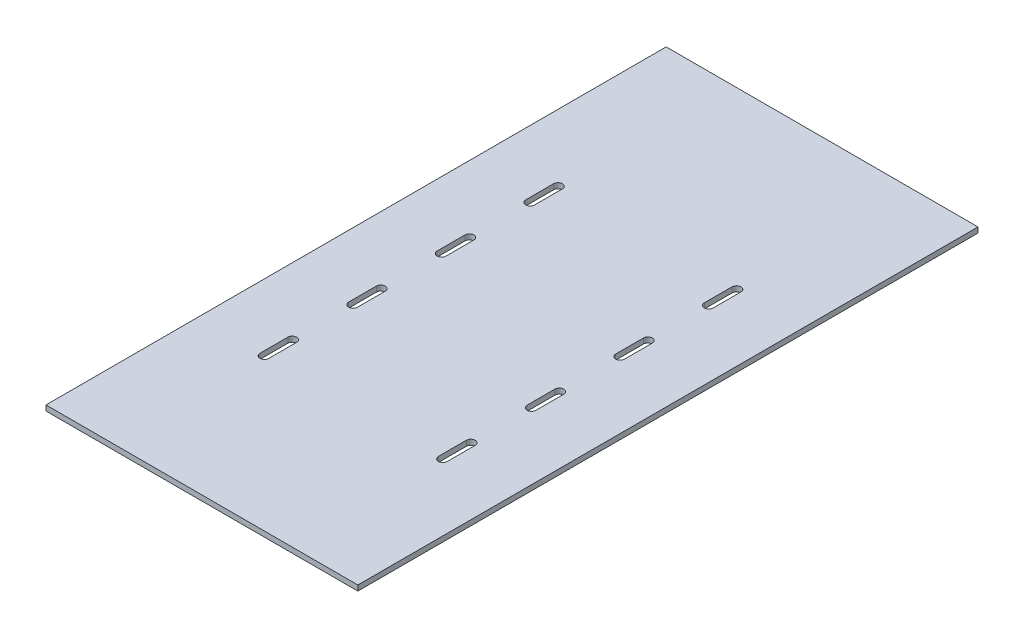
SolidWorks part; units mm, degrees
ref_plane "Front Plane" through (0, 0, 0) normal (0, 0, 1) x (1, 0, 0)
ref_plane "Top Plane" through (0, 0, 0) normal (0, 1, 0) x (1, 0, 0)
ref_plane "Right Plane" through (0, 0, 0) normal (1, 0, 0) x (0, 0, -1)
sketch "Sketch1" plane through (0, 0, 0) normal (0, 1, 0) x (1, 0, 0)
  line L1 (0, 0) -> (176, 0)
  line L2 (0, 0) -> (0, 350)
  line L3 (0, 350) -> (176, 350)
  line L4 (176, 0) -> (176, 350)
  dimension "D1" = 350
  dimension "D2" = 176
extrude "Boss-Extrude1" add sketch "Sketch1" along normal blind 3
sketch "Sketch2" plane through (0, 3, 0) normal (0, 1, 0) x (1, 0, 0)
  line L0 (176, 0) -> (176, 70)
  line L1 (176, 0) -> (176, 350) construction
  line L2 (176, 70) -> (88, 70)
  line L3 (176, 70) -> (176, 120)
  line L4 (176, 120) -> (176, 170)
  line L5 (176, 170) -> (176, 220)
  line L6 (176, 120) -> (88, 120)
  line L7 (176, 170) -> (88, 170)
  line L8 (176, 220) -> (88, 220)
  line L9 (88, 70) -> (88, 93.5)
  line L10 (88, 120) -> (88, 143.5)
  line L11 (88, 170) -> (88, 193.5)
  line L12 (88, 220) -> (88, 243.5)
hole_wizard "Ø5.0mm Dowel Slot1" positions "Sketch5" profile "Sketch4" size "Ø5.0" standard "ANSI Metric" slot yes end condition through all
sketch "Sketch5" plane through (0, 3, 0) normal (0, 1, 0) x (1, 0, 0)
  line L0 (138.375, 103.85) -> (138.375, 83.15) construction
  point P0 (138.375, 93.5)
  point P6 (37.625, 93.5)
  point P9 (138.375, 143.5)
  point P12 (37.625, 143.5)
  point P15 (37.625, 193.5)
  point P18 (138.375, 193.5)
  point P21 (138.375, 243.5)
  point P24 (37.625, 243.5)
  dimension "D1" = 20.7
sketch "Sketch4" plane through (138.375, 3, -93.5) normal (1, 0, 0) x (0, 0, 1)
  line L0 (0, 0) -> (0, 3)
  line L1 (0, 3) -> (2.5, 3)
  line L2 (2.5, 3) -> (2.5, 0)
  line L5 (2.5, 0) -> (0, 0)
  line L11 (0, -6.35) -> (0, 107.95) construction
  dimension "Thru Hole Dia." = 5
  dimension "Thru Hole Depth" = 3
